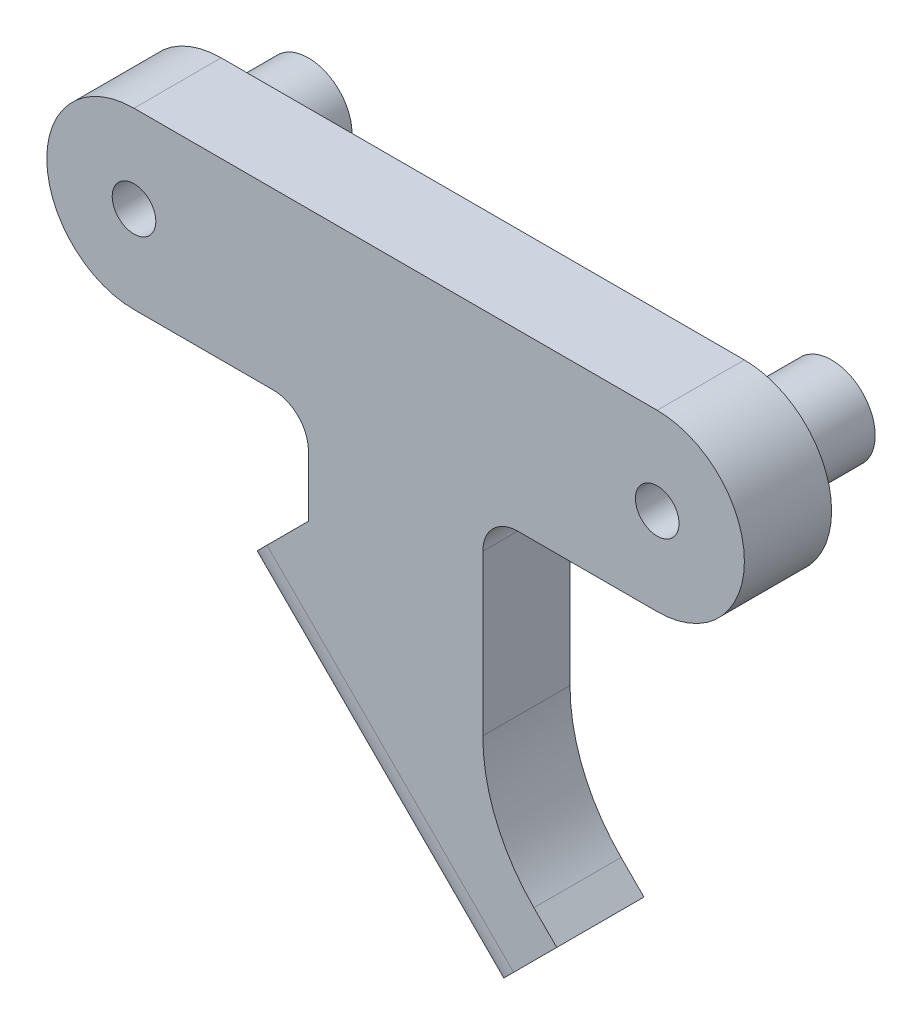
SolidWorks part; units mm, degrees
ref_plane "Piano frontale" through (0, 0, 0) normal (0, 0, 1) x (1, 0, 0)
ref_plane "Piano superiore" through (0, 0, 0) normal (0, 1, 0) x (1, 0, 0)
ref_plane "Piano destro" through (0, 0, 0) normal (1, 0, 0) x (0, 0, -1)
sketch "Schizzo1" plane through (0, 0, 0) normal (0, 0, 1) x (1, 0, 0)
  line L1 (-13.208, 5) -> (16.792, 5)
  line L2 (-13.208, -5) -> (-3.208, -5)
  line L3 (6.792, -28.7941) -> (6.792, -18.7941)
  line L4 (-3.208, -18.7941) -> (6.792, -28.7941)
  line L5 (6.792, -5) -> (16.792, -5)
  line L7 (-3.208, -5) -> (-3.208, -18.7941)
  line L9 (6.792, -5) -> (6.792, -18.7941)
  line L10 (6.792, 0) -> (16.792, 0) construction
  arc A0 (-13.208, 5) -> (-13.208, -5) centre (-13.208, 0) ccw
  arc A1 (16.792, -5) -> (16.792, 5) centre (16.792, 0) ccw
  point P3 (1.792, 0)
  dimension "D1" = 30
  dimension "D2" = 10
  dimension "D3" = 10
  dimension "D4" = 10
extrude "Estrusione-Estrusione3" add sketch "Schizzo1" along normal blind 5 contours L2 L7 L4 L3 L9 L5 A1 L1 A0
sketch "Schizzo3" plane through (0, 0, 0) normal (0, 0, -1) x (-1, 0, 0)
  line L6 (13.208, 5) -> (-16.792, 5)
  line L7 (-16.792, -5) -> (-6.792, -5)
  line L8 (-6.792, -5) -> (-6.792, -28.7941)
  line L9 (-6.792, -28.7941) -> (3.208, -18.7941)
  line L10 (3.208, -18.7941) -> (3.208, -5)
  line L11 (3.208, -5) -> (13.208, -5)
  line L12 (13.208, 5) -> (-16.792, 5) construction
  line L13 (-16.792, -5) -> (-6.792, -5) construction
  line L14 (-6.792, -5) -> (-6.792, -28.7941) construction
  line L15 (-6.792, -28.7941) -> (3.208, -18.7941) construction
  line L16 (3.208, -18.7941) -> (3.208, -5) construction
  line L17 (3.208, -5) -> (13.208, -5) construction
  circle A0 centre (-16.792, 0) radius 2.5
  circle A1 centre (13.208, 0) radius 2.5
  arc A2 (13.208, -5) -> (13.208, 5) centre (13.208, 0) ccw
  arc A3 (-16.792, 5) -> (-16.792, -5) centre (-16.792, 0) ccw
  arc A4 (13.208, -5) -> (13.208, 5) centre (13.208, 0) ccw construction
  arc A5 (-16.792, 5) -> (-16.792, -5) centre (-16.792, 0) ccw construction
  dimension "D1" = 0
extrude "Estrusione-Estrusione4" add sketch "Schizzo3" along normal blind 5
ref_plane "Piano1" through (17.7931, -17.7931, 0) normal (-0.7071, 0.7071, 0) x (0, 0, -1)
sketch "Schizzo7" plane through (17.7931, -17.7931, 0) normal (-0.7071, 0.7071, 0) x (0, 0, -1)
  line L0 (-5, 15.5578) -> (-5, -1.2671) construction
  line L1 (0, 15.5578) -> (-5, 15.5578)
  line L2 (0, 15.5578) -> (0, 9.5578)
  line L3 (0, 9.5578) -> (-5, 9.5578)
  line L4 (-5, 15.5578) -> (-5, 9.5578)
  dimension "D1" = 6
extrude "Estrusione-Estrusione5" add sketch "Schizzo7" along normal blind 20
sketch "Schizzo6" plane through (17.7931, -17.7931, 0) normal (-0.7071, 0.7071, 0) x (0, 0, -1)
  line L0 (0, -1.2671) -> (0, 9.5578) construction
  line L1 (-5, 15.5578) -> (0, 15.5578) construction
  circle A0 centre (-2.5, 12.5578) radius 1.65
  dimension "D1" = 3.3
  dimension "D2" = 2.5
  dimension "D3" = 3
extrude "Taglio-Estrusione1" cut sketch "Schizzo6" along normal up to surface (20 mm away) up to face at (-5.2791, -12.5809, 2.5)
fillet "Raccordo1" radius 2.5 2 edges at (-0.2791, -21.723, 0) (-0.2791, -21.723, 5)
sketch "Schizzo8" plane through (0, 0, -5) normal (0, 0, -1) x (-1, 0, 0)
  circle A0 centre (-16.792, 0) radius 1.25
  circle A1 centre (13.208, 0) radius 1.25
  dimension "D1" = 2.5
extrude "Taglio-Estrusione2" cut sketch "Schizzo8" against normal through all
fillet "Raccordo2" radius 2 2 edges at (-3.208, -5, 2.5) (6.792, -5, 2.5)
fillet "Raccordo3" radius 10 1 edges at (6.792, -20.3088, 2.5)
ref_axis "Assi1" through (-5.2288, -12.5306, 2.5) along (0.7071, -0.7071, 0)
ref_point "Punto1"
ref_axis "Assi2" through (11.0346, -24.5515, 5) along (0, 0, -1)
ref_point "Punto2"
ref_axis "Assi3" through (16.792, 0, 5) along (0, 0, -1)
ref_axis "Assi4" through (6.792, -7, 0) along (0, -1, 0)
ref_point "Punto3"
